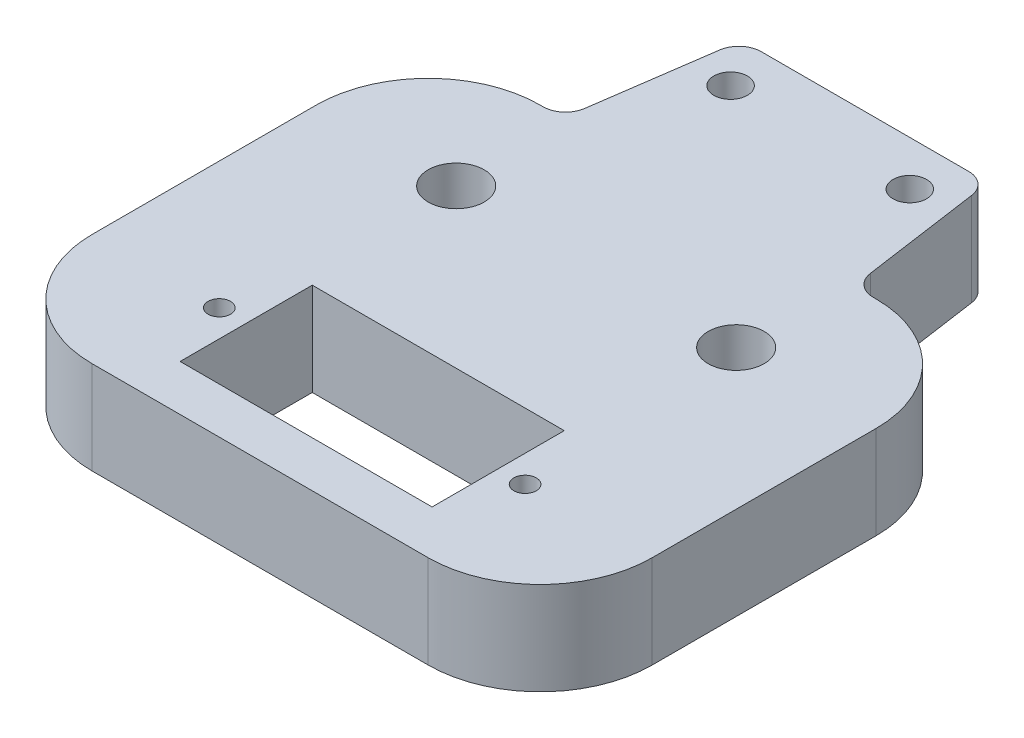
SolidWorks part; units mm, degrees
ref_plane "Front Plane" through (0, 0, 0) normal (0, 0, 1) x (1, 0, 0)
ref_plane "Top Plane" through (0, 0, 0) normal (0, 1, 0) x (1, 0, 0)
ref_plane "Right Plane" through (0, 0, 0) normal (1, 0, 0) x (0, 0, -1)
sketch "Sketch1" plane through (0, 0, 0) normal (0, 1, 0) x (1, 0, 0)
  line L0 (-13, 20) -> (13, 20) construction
  line L1 (-15, 20) -> (-13, 20)
  line L2 (-25, 10) -> (-25, -10)
  line L3 (-15, -20) -> (15, -20)
  line L4 (25, 10) -> (25, -10)
  line L5 (-25, 20) -> (25, -20) construction
  line L6 (-25, -20) -> (25, 20) construction
  line L7 (13, 20) -> (15, 20)
  line L8 (-12.5, 10) -> (12.5, 10) construction
  line L9 (0, -10) -> (0, 0) construction
  line L10 (-11.25, -4.1) -> (11.25, -4.1)
  line L11 (-11.25, -4.1) -> (-11.25, -15.9)
  line L12 (-11.25, -15.9) -> (11.25, -15.9)
  line L13 (11.25, -4.1) -> (11.25, -15.9)
  line L14 (-11.25, -4.1) -> (11.25, -15.9) construction
  line L15 (-11.25, -15.9) -> (11.25, -4.1) construction
  line L16 (-13.65, -10) -> (13.65, -10) construction
  line L17 (0, 34) -> (0, 20) construction
  line L18 (-13, 20) -> (-11, 34)
  line L21 (11, 34) -> (13, 20)
  line L22 (-11, 34) -> (11, 34)
  line L23 (-8, 30) -> (8, 30) construction
  arc A0 (15, -20) -> (25, -10) centre (15, -10) ccw
  arc A1 (15, 20) -> (25, 10) centre (15, 10) cw
  arc A2 (-25, -10) -> (-15, -20) centre (-15, -10) ccw
  arc A3 (-15, 20) -> (-25, 10) centre (-15, 10) ccw
  circle A4 centre (-12.5, 10) radius 2.5
  circle A5 centre (12.5, 10) radius 2.5
  circle A6 centre (13.65, -10) radius 1
  circle A7 centre (-13.65, -10) radius 1
  circle A8 centre (8, 30) radius 1.5
  circle A9 centre (-8, 30) radius 1.5
  point P0 (0, 0)
  point P32 (0, -10)
  point P43 (0, 30)
  dimension "D6" = 10
  dimension "D10" = 5
  dimension "D16" = 2
  dimension "D7" = 3
  dimension "D1" = 50
  dimension "D2" = 40
  dimension "D3" = 2
  dimension "D4" = 14
  dimension "D5" = 22
  dimension "D8" = 10
  dimension "D9" = 16
  dimension "D11" = 25
  dimension "D12" = 22.5
  dimension "D13" = 11.8
  dimension "D14" = 10
  dimension "D15" = 2.4
extrude "Boss-Extrude1" add sketch "Sketch1" along normal blind 8.3 contours L1 A3 L2 A2 L3 A0 L4 A1 L7 L10 L13 L12 L11 A4 A5 A6 A7 region at (0, 0, -5.6664)
fillet "Fillet1" radius 2 4 edges at (13, 4.15, -20) (11, 4.15, -34) (-13, 4.15, -20) (-11, 4.15, -34)
